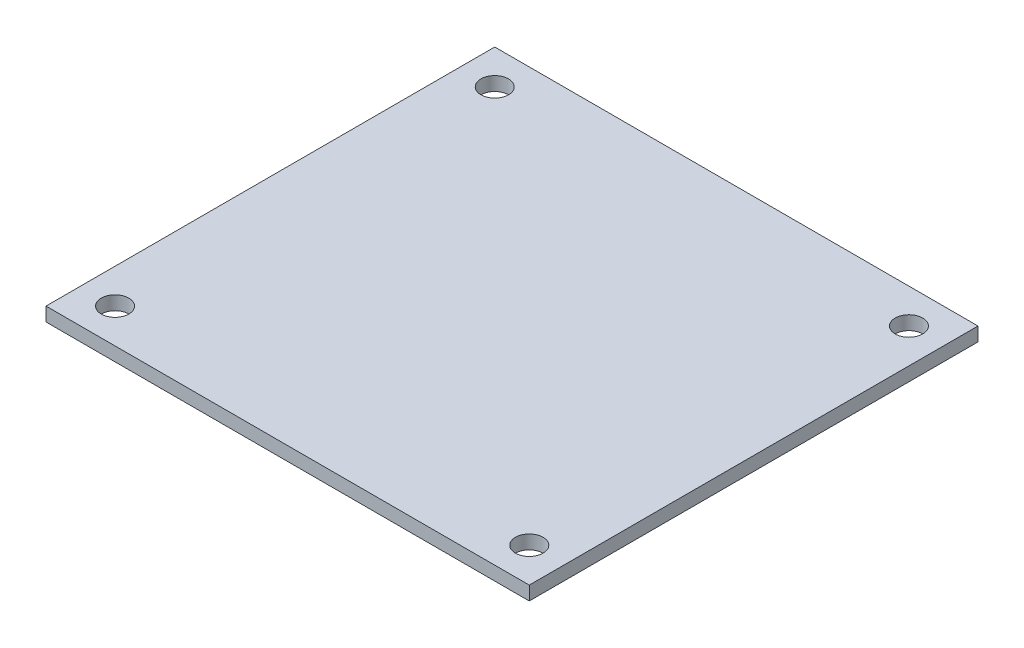
SolidWorks part; units mm, degrees
ref_plane "Front Plane" through (0, 0, 0) normal (0, 0, 1) x (1, 0, 0)
ref_plane "Top Plane" through (0, 0, 0) normal (0, 1, 0) x (1, 0, 0)
ref_plane "Right Plane" through (0, 0, 0) normal (1, 0, 0) x (0, 0, -1)
sketch "Sketch1" plane through (0, 0, 0) normal (0, 1, 0) x (1, 0, 0)
  line L1 (0, 0) -> (177.8, 0)
  line L2 (0, 0) -> (0, -165.1)
  line L3 (0, -165.1) -> (177.8, -165.1)
  line L4 (177.8, 0) -> (177.8, -165.1)
extrude "Boss-Extrude1" add sketch "Sketch1" along normal blind 5.08
ref_axis "Axis1" through (88.9, 5.08, 165.1) along (0, 0, -1)
ref_axis "Axis2" through (0, 5.08, 82.55) along (1, 0, 0)
ref_plane "Plane3" through (0, 0, 82.55) normal (0, 0, 1) x (1, 0, 0)
ref_plane "Plane4" through (88.9, 0, 0) normal (-1, 0, 0) x (0, 0, 1)
sketch "Sketch3" plane through (0, 5.08, 0) normal (0, 1, 0) x (1, 0, 0)
  circle A0 centre (12.7, -12.7) radius 5.08
extrude "Cut-Extrude1" cut sketch "Sketch3" against normal blind 5.08
mirror "Mirror1" about plane through (88.9, 0, 0) normal (-1, 0, 0) of "Cut-Extrude1"
mirror "Mirror2" about plane through (0, 0, 82.55) normal (0, 0, 1) of "Mirror1"
sketch "Sketch4" plane through (0, 0, 0) normal (0, -1, 0) x (-1, 0, 0)
  text T0 "Ben Phung & Joaquin Gonzalez-Salgado"
extrude "Cut-Extrude2" cut sketch "Sketch4" against normal blind 0.254
